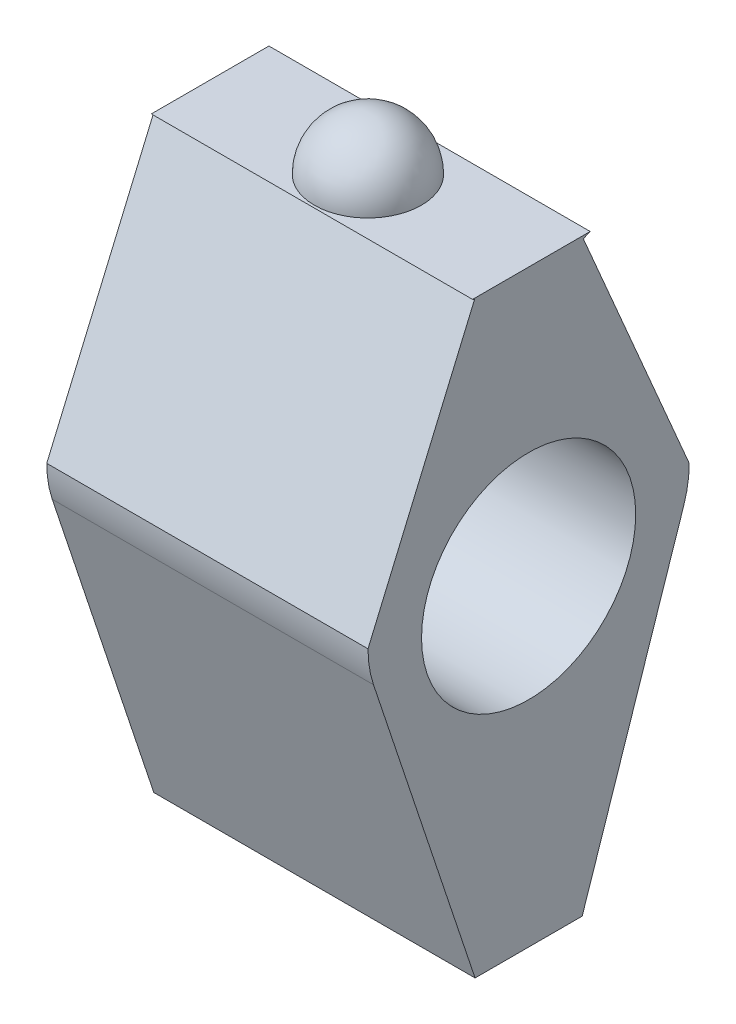
SolidWorks part; units mm, degrees
ref_plane "Front Plane" through (0, 0, 0) normal (0, 0, 1) x (1, 0, 0)
ref_plane "Top Plane" through (0, 0, 0) normal (0, 1, 0) x (1, 0, 0)
ref_plane "Right Plane" through (0, 0, 0) normal (1, 0, 0) x (0, 0, -1)
sketch "Sketch1" plane through (0, 0, 0) normal (0, 0, 1) x (1, 0, 0)
  line L1 (-38.1, 76.2) -> (38.1, 76.2)
  line L2 (-38.1, 76.2) -> (-38.1, -76.2)
  line L3 (-38.1, -76.2) -> (38.1, -76.2)
  line L4 (38.1, 76.2) -> (38.1, -76.2)
extrude "Boss-Extrude1" add sketch "Sketch1" along normal blind 76.2
sketch "Sketch2" plane through (38.1, 0, 0) normal (1, 0, 0) x (0, 0, -1)
  line L0 (0, -76.2) -> (0, 76.2) construction
  circle A0 centre (-38.1, 0) radius 25.4
  dimension "D1" = 50.8
  dimension "D2" = 38.1
extrude "Cut-Extrude1" cut sketch "Sketch2" against normal blind 101.6
sketch "Sketch3" plane through (38.1, 0, 0) normal (1, 0, 0) x (0, 0, -1)
  line L0 (-76.2, 0) -> (-50.8, -76.2)
  line L2 (-76.2, -76.2) -> (0, -76.2) construction
  line L5 (0, 0) -> (-25.4, -76.2)
  line L7 (-76.2, -76.2) -> (-76.2, 76.2) construction
  line L8 (0, -76.2) -> (0, 76.2) construction
  line L9 (-76.2, 0) -> (-76.2, -76.2)
  line L10 (-76.2, -76.2) -> (-50.8, -76.2)
  line L11 (-25.4, -76.2) -> (0, -76.2)
  line L12 (0, -76.2) -> (0, 0)
  dimension "D2" = 25.4
  dimension "D3" = 25.4
extrude "Cut-Extrude2" cut sketch "Sketch3" against normal through all
fillet "Fillet1" radius 25.4 2 edges at (0, 0, 0) (0, 0, 76.2)
sketch "Sketch4" plane through (0, 76.2, 0) normal (0, 1, 0) x (1, 0, 0)
  line L1 (-38.1, 0) -> (38.1, 0)
  line L2 (-38.1, 0) -> (-38.1, -76.2)
  line L3 (-38.1, -76.2) -> (38.1, -76.2)
  line L4 (38.1, 0) -> (38.1, -76.2)
  circle A0 centre (0, -38.1234) radius 12.7
  dimension "D1" = 25.4
extrude "Cut-Extrude3" cut sketch "Sketch4" against normal blind 12.7
fillet "Fillet2" radius 12.7 1 edges at (0, 76.2, 50.8234)
sketch "Sketch5" plane through (0, 63.5, 0) normal (0, 1, 0) x (1, 0, 0)
  line L0 (-38.1, -50.8234) -> (38.1, -50.8234) construction
  line L1 (-38.1, 0) -> (-38.1, -76.2) construction
  line L2 (38.1, -76.2) -> (38.1, 0) construction
  line L3 (-38.1, -25.4234) -> (38.1, -25.4234) construction
  circle A0 centre (0, -38.1234) radius 12.7 construction
ref_plane "Plane1" through (0, 28.173, 65.9212) normal (0, -0.393, -0.9195) x (-1, 0, 0)
sketch "Sketch6" plane through (0, 28.173, 65.9212) normal (0, -0.393, -0.9195) x (-1, 0, 0)
  line L1 (-41.8518, 38.1912) -> (42.0611, 38.1912)
  line L2 (-41.8518, 38.1912) -> (-41.8518, -65.6013)
  line L3 (-41.8518, -65.6013) -> (42.0611, -65.6013)
  line L4 (42.0611, 38.1912) -> (42.0611, -65.6013)
extrude "Cut-Extrude4" cut sketch "Sketch6" against normal blind 25.4
ref_plane "Plane2" through (0, 0.6386, -1.4914) normal (0, 0.3936, -0.9193) x (-1, 0, 0)
sketch "Sketch7" plane through (0, 0.6386, -1.4914) normal (0, 0.3936, -0.9193) x (-1, 0, 0)
  line L1 (-39.7726, 67.6236) -> (41.0319, 67.6236)
  line L2 (-39.7726, 67.6236) -> (-39.7726, -29.9715)
  line L3 (-39.7726, -29.9715) -> (41.0319, -29.9715)
  line L4 (41.0319, 67.6236) -> (41.0319, -29.9715)
extrude "Cut-Extrude5" cut sketch "Sketch7" along normal blind 25.4
sketch "Sketch8" plane through (0, 63.5, 0) normal (0, 1, 0) x (1, 0, 0)
  line L1 (-38.1, -25.4234) -> (38.1, -25.4234)
  line L2 (-38.1, -25.4234) -> (-38.1, -51.4006)
  line L3 (-38.1, -51.4006) -> (38.1, -51.4006)
  circle A0 centre (0, -38.1234) radius 12.7
